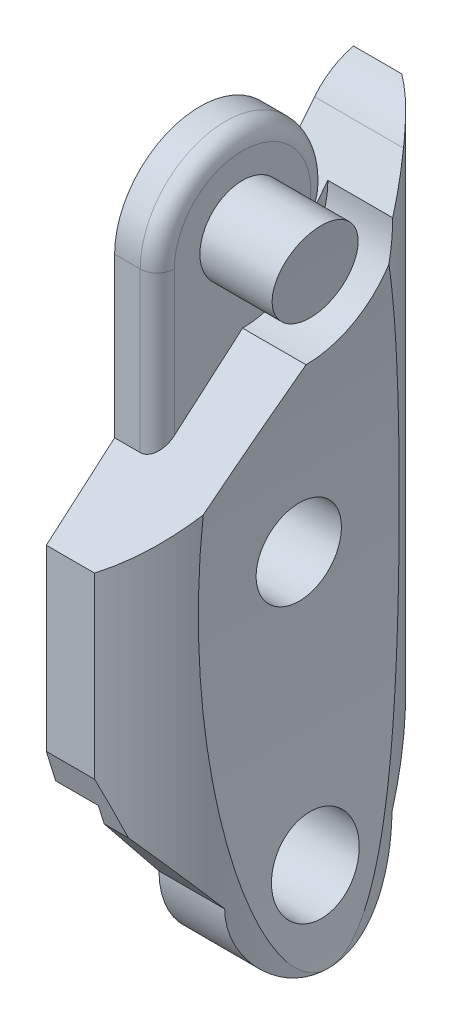
SolidWorks part; units mm, degrees
ref_plane "Front Plane" through (0, 0, 0) normal (0, 0, 1) x (1, 0, 0)
ref_plane "Top Plane" through (0, 0, 0) normal (0, 1, 0) x (1, 0, 0)
ref_plane "Right Plane" through (0, 0, 0) normal (1, 0, 0) x (0, 0, -1)
sketch "Sketch1" plane through (0, 0, 0) normal (0, 1, 0) x (1, 0, 0)
  line L0 (-6.3246, 9) -> (6.3246, 9)
  line L1 (-6.3246, -9) -> (6.3246, -9)
  arc A0 (-6.3246, 9) -> (-6.3246, -9) centre (0, 0) ccw
  arc A1 (6.3246, 9) -> (6.3246, -9) centre (0, 0) cw
  point P9 (-11, 0)
  point P10 (11, 0)
  dimension "D1" = 22
  dimension "D2" = 18
extrude "Boss-Extrude1" add sketch "Sketch1" along normal blind 40
sketch "Sketch2" plane through (0, 0, 0) normal (0, -1, 0) x (1, 0, 0)
  line L0 (1.5, 5) -> (-1.5, 5)
  line L1 (1.5, -5) -> (-1.5, -5)
  line L2 (0, -5) -> (0, 5) construction
  arc A2 (-1.5, 5) -> (1.5, 5) centre (0, 5) cw
  arc A3 (-1.5, -5) -> (1.5, -5) centre (0, -5) ccw
  dimension "D1" = 1.5
  dimension "D2" = 10
extrude "Cut-Extrude1" cut sketch "Sketch2" against normal blind 45
sketch "Sketch3" plane through (0, 0, -9) normal (0, 0, -1) x (-1, 0, 0)
  line L0 (6, 0) -> (6, 10)
  line L1 (6, 10) -> (-6, 10)
  line L2 (-6, 10) -> (-6, 0)
  line L3 (6, 0) -> (-6, 0)
  line L4 (-6.3246, 0) -> (6.3246, 0) construction
  point P10 (0, 0)
  dimension "D1" = 12
  dimension "D2" = 10
extrude "Cut-Extrude2" cut sketch "Sketch3" against normal up to surface (18 mm away) up to face at (0, 20, 9)
sketch "Sketch4" plane through (6, 0, 0) normal (-1, 0, 0) x (0, 0, 1)
  line L0 (-9, 10) -> (-4.9, 4.9)
  line L1 (9, 10) -> (4.9, 4.9)
  line L2 (9, 0) -> (-9, 0) construction
  line L3 (-9, 10) -> (-10.2904, -1.9304)
  line L4 (-10.2904, -1.9304) -> (12.0438, -1.9304)
  line L6 (9, 40) -> (9, 0) construction
  line L7 (12.0438, -1.9304) -> (9, 10)
  line L8 (-9, 40) -> (-9, 0) construction
  arc A0 (-4.9, 4.9) -> (4.9, 4.9) centre (0, 4.9) ccw
  circle A1 centre (0, 4.9) radius 2.55
  point P7 (0, 0)
  dimension "D1" = 5.1
  dimension "D2" = 4.9
  dimension "D3" = 10
extrude "Cut-Extrude3" cut sketch "Sketch4" against normal mid plane 35
fillet "Fillet4" radius 2 4 edges at (0, 10, 6.5) (0, 10, 5) (0, 10, -5) (0, 10, -6.5)
ref_plane "Plane1" through (-6.3246, 0, 0) normal (-1, 0, 0) x (0, 0, 1)
sketch "Sketch6" plane through (-6.3246, 0, 0) normal (-1, 0, 0) x (0, 0, 1)
  line L0 (9, 22.2324) -> (0, 30)
  line L1 (9, 40) -> (9, 10) construction
  line L2 (-5, 35) -> (-6.7156, 37.1341)
  line L3 (9, 40) -> (-9, 40) construction
  line L7 (-9, 38.5679) -> (-20.9852, 70.2973)
  line L8 (4.9, 4.9) -> (9, 10) construction
  line L9 (-9, 10) -> (-4.9, 4.9) construction
  line L10 (-9, 40) -> (-9, 10) construction
  line L11 (-20.9852, 70.2973) -> (29.8275, 37.5947)
  line L12 (29.8275, 37.5947) -> (9, 22.2324)
  arc A0 (0, 30) -> (-5, 35) centre (0, 35) cw
  circle A1 centre (0, 35) radius 2.5
  arc A2 (-6.7156, 37.1341) -> (-9, 38.5679) centre (-9.9296, 34.5502) ccw
  point P7 (0, 0)
  point P8 (0, 0)
  dimension "D1" = 5
  dimension "D3" = 5
  dimension "D2" = 5
  dimension "D4" = 9
  dimension "D5" = 92
  dimension "D6" = 2.7382
  dimension "D7" = 1.4321
extrude "Cut-Extrude5" cut sketch "Sketch6" against normal blind 9.6 from surface starting at face at (6, 4.9, -2.55)
extrude "Cut-Extrude6" cut sketch "Sketch6<3>" along normal blind 6.604 from surface starting at face at (-6, 4.9, 2.55)
sketch "Sketch6<3>" plane through (-6.3246, 0, 0) normal (-1, 0, 0) x (0, 0, 1) same geometry as "Sketch6"
sketch "Sketch7" plane through (6, 0, 0) normal (1, 0, 0) x (0, 0, -1)
  line L0 (5, 35) -> (6.7156, 37.1341)
  line L2 (17.9055, 46.1898) -> (-20.6283, 40.1522)
  line L3 (-9, 40) -> (9, 40) construction
  line L4 (-5, 35) -> (-5, 25.6846)
  line L6 (-5, 25.6846) -> (-9, 22.2324)
  line L7 (-9, 22.2324) -> (-20.6283, 40.1522)
  line L8 (-9, 22.2324) -> (0, 30) construction
  line L9 (9, 38.5679) -> (17.9055, 46.1898)
  arc A0 (5, 35) -> (-5, 35) centre (0, 35) ccw
  arc A1 (6.7156, 37.1341) -> (9, 38.5679) centre (9.9296, 34.5502) cw
  arc A2 (9, 38.5679) -> (6.7156, 37.1341) centre (9.9296, 34.5502) ccw construction
  dimension "D1" = 5
extrude "Cut-Extrude7" cut sketch "Sketch7" against normal blind 14.986
sketch "Sketch16" plane through (-6.3246, 0, 0) normal (-1, 0, 0) x (0, 0, 1)
  line L0 (8.1133, 8.897) -> (11.5501, 20.0314)
  line L1 (11.5501, 20.0314) -> (18.056, 15.6952)
  line L2 (18.056, 15.6952) -> (16.1561, 2.2816)
  line L3 (16.1561, 2.2816) -> (8.1133, 8.897)
  line L4 (4.9, 4.9) -> (9, 10) construction
  line L5 (9, 22.2324) -> (0, 30) construction
extrude "Cut-Extrude14" cut sketch "Sketch16" against normal blind 20 and the other way blind 10
sketch "Sketch17" plane through (0, 0, 0) normal (0, 0, 1) x (1, 0, 0)
  line L0 (11, 0) -> (25.5755, 70.0547)
  line L1 (25.5755, 70.0547) -> (-19.117, 73.0805)
  line L2 (-19.117, 73.0805) -> (-22.1033, 10.057)
  line L3 (-22.1033, 10.057) -> (-11, 0)
  line L4 (6, 40) -> (-6, 40) construction
  line L5 (-11, 40) -> (-11, 54.7093)
  line L6 (-11, 54.7093) -> (1.0392, 61.7822)
  line L7 (1.0392, 61.7822) -> (17.2773, 53.9279)
  line L8 (17.2773, 53.9279) -> (11, 40)
  arc A0 (-11, 0) -> (-11, 40) centre (-127.2927, 20) ccw
  arc A2 (11, 40) -> (11, 0) centre (127.2927, 20) ccw
  dimension "D1" = 118
sketch "Sketch19" plane through (0, 0, 5) normal (0, 0, 1) x (1, 0, 0)
  line L1 (3.5, 74.9368) -> (-30.892, 74.9368)
  line L2 (3.5, 74.9368) -> (3.5, -5.5321)
  line L3 (3.5, -5.5321) -> (-30.892, -5.5321)
  line L4 (-30.892, 74.9368) -> (-30.892, -5.5321)
fillet "Fillet3" radius 1 4 edges at (6, 40, 0) (6, 30.3423, 5) (-6, 40, 0) (-6, 30.3423, 5)
extrude "Cut-Extrude17" cut sketch "Sketch19" against normal blind 31 and the other way blind 9 contours L2 L3 L4 L1
sketch "Sketch20" plane through (3.5, 0, 0) normal (-1, 0, 0) x (0, 0, 1)
  line L0 (-9, 10) -> (8.4537, 10) construction
  circle A0 centre (0, 20.3) radius 3.25
  dimension "D1" = 6.5
  dimension "D2" = 10.3
extrude "Boss-Extrude2" add sketch "Sketch20" along normal blind 2
sketch "Sketch21" plane through (1.5, 0, 0) normal (-1, 0, 0) x (0, 0, 1)
  circle A0 centre (0, 20.3) radius 1.5
  circle A1 centre (0, 20.3) radius 3.25 construction
  dimension "D1" = 3
extrude "Cut-Extrude18" cut sketch "Sketch21" against normal blind 14
sketch "Sketch22" plane through (1.5, 0, 0) normal (-1, 0, 0) x (0, 0, 1)
  circle A0 centre (0, 20.3) radius 2.5
  dimension "D1" = 5
extrude "Cut-Extrude19" cut sketch "Sketch22" against normal blind 14 from offset 4 offset against normal yes
extrude "Cut-Extrude20" cut sketch "Sketch17" against normal blind 14 and the other way blind 14
